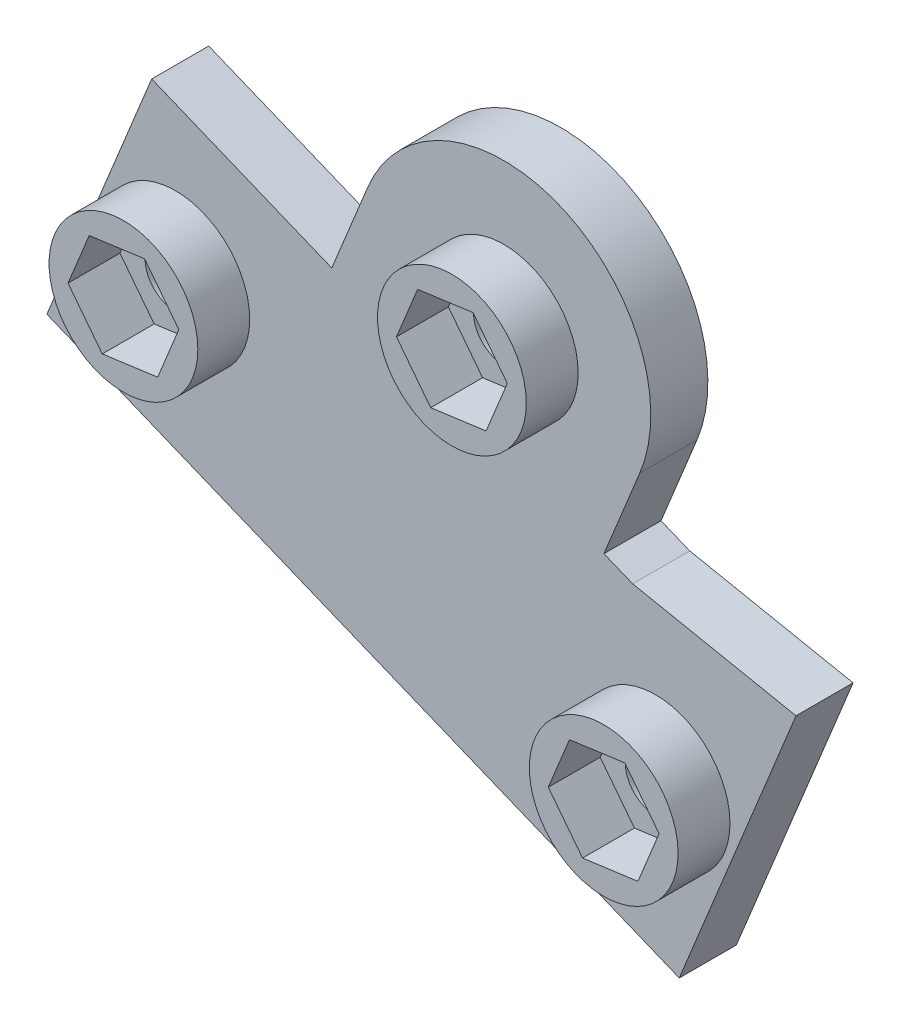
SolidWorks part; units mm, degrees
ref_plane "Front Plane" through (0, 0, 0) normal (0, 0, 1) x (1, 0, 0)
ref_plane "Top Plane" through (0, 0, 0) normal (0, 1, 0) x (1, 0, 0)
ref_plane "Right Plane" through (0, 0, 0) normal (1, 0, 0) x (0, 0, -1)
sketch "Sketch1" plane through (0, 0, 0) normal (0, 0, 1) x (1, 0, 0)
  line L0 (-67.8672, -11.1468) -> (-69.9439, -16.2233)
  line L1 (-52.1328, -17.5832) -> (-54.2095, -22.6598)
  line L2 (-86.4142, -26.7728) -> (-80.3564, -11.9639)
  line L3 (-49.8549, -41.7281) -> (-43.1038, -25.2247)
  line L6 (-68.0868, -16.983) -> (-80.5878, -11.8693)
  line L7 (-80.5878, -11.8693) -> (-86.6456, -26.6781)
  line L8 (-86.6456, -26.6781) -> (-49.6235, -41.8228)
  line L9 (-49.6235, -41.8228) -> (-42.8541, -25.2745)
  line L10 (-42.8541, -25.2745) -> (-52.5473, -23.3398)
  line L11 (-52.5473, -23.3398) -> (-56.0666, -21.9001)
  line L12 (-68.0868, -16.983) -> (-80.5878, -11.8693)
  line L13 (-80.5878, -11.8693) -> (-86.6456, -26.6781)
  line L14 (-86.6456, -26.6781) -> (-49.6235, -41.8228)
  line L15 (-49.6235, -41.8228) -> (-42.8541, -25.2745)
  line L16 (-42.8541, -25.2745) -> (-52.5473, -23.3398)
  line L17 (-52.5473, -23.3398) -> (-56.0666, -21.9001)
  circle A0 centre (-78.9889, -21.1668) radius 1.75 construction
  arc A1 (-68.0868, -16.983) -> (-56.0666, -21.9001) centre (-60, -14.365) ccw
  arc A2 (-68.0868, -16.983) -> (-56.0666, -21.9001) centre (-60, -14.365) ccw
  circle A3 centre (-51.2223, -32.5253) radius 1.75 construction
  circle A4 centre (-78.9889, -21.1668) radius 1.75
  circle A5 centre (-51.2223, -32.5253) radius 1.75
  circle A6 centre (-60, -14.365) radius 1.75
  circle A7 centre (-60, -14.365) radius 8.5
  dimension "D2" = 0.25
  dimension "D3" = 0.25
  dimension "D1" = 0
extrude "Boss-Extrude1" add sketch "Sketch1" along normal blind 3.3 contours A7 A2 A6 | A7 L0 L12 | A2 L12 L2 L14 L3 L16 L17 A5 A4 | A7 L17 L1 region at (-68.8941, -15.2085, 0) region at (-58.4065, -6.2606, 0) region at (-64.9518, -27.1084, 0) region at (-54.2471, -21.2002, 0)
sketch "Sketch2" plane through (0, 0, 0) normal (0, 0, -1) x (-1, 0, 0)
  circle A0 centre (60, -14.365) radius 4.1
  circle A1 centre (60, -14.365) radius 1.75 construction
  circle A2 centre (60, -14.365) radius 1.75
  dimension "D1" = 8.2
extrude "Boss-Extrude2" add sketch "Sketch2" along normal blind 0.2
sketch "Sketch3" plane through (0, 0, 3.3) normal (0, 0, 1) x (1, 0, 0)
  line L0 (-86.4142, -26.7728) -> (-80.3564, -11.9639) construction
  line L1 (-77.7648, -18.1743) -> (-80.9684, -18.6104)
  line L2 (-80.9684, -18.6104) -> (-82.1925, -21.6029)
  line L3 (-82.1925, -21.6029) -> (-80.213, -24.1592)
  line L4 (-80.213, -24.1592) -> (-77.0094, -23.7231)
  line L5 (-77.0094, -23.7231) -> (-75.7853, -20.7307)
  line L6 (-75.7853, -20.7307) -> (-77.7648, -18.1743)
  line L7 (-49.8549, -41.7281) -> (-43.1038, -25.2247) construction
  line L8 (-52.4464, -35.5177) -> (-49.2428, -35.0816)
  line L9 (-49.2428, -35.0816) -> (-48.0187, -32.0892)
  line L10 (-48.0187, -32.0892) -> (-49.9982, -29.5328)
  line L11 (-49.9982, -29.5328) -> (-53.2018, -29.9689)
  line L12 (-53.2018, -29.9689) -> (-54.4259, -32.9614)
  line L13 (-54.4259, -32.9614) -> (-52.4464, -35.5177)
  line L14 (-67.8672, -11.1468) -> (-69.9439, -16.2233) construction
  line L15 (-61.2241, -17.3575) -> (-58.0205, -16.9214)
  line L16 (-58.0205, -16.9214) -> (-56.7964, -13.9289)
  line L17 (-56.7964, -13.9289) -> (-58.7759, -11.3725)
  line L18 (-58.7759, -11.3725) -> (-61.9795, -11.8086)
  line L19 (-61.9795, -11.8086) -> (-63.2036, -14.8011)
  line L20 (-63.2036, -14.8011) -> (-61.2241, -17.3575)
  circle A0 centre (-78.9889, -21.1668) radius 2.8 construction
  circle A1 centre (-51.2223, -32.5253) radius 2.8 construction
  circle A2 centre (-60, -14.365) radius 2.8 construction
  circle A3 centre (-78.9889, -21.1668) radius 4.3
  circle A4 centre (-60, -14.365) radius 4.3
  circle A5 centre (-51.2223, -32.5253) radius 4.3
  dimension "D2" = 8.6
  dimension "D1" = 5.6
extrude "Boss-Extrude3" add sketch "Sketch3" along normal blind 3 contours A3 L6 L5 L4 L3 L2 L1 | A4 L20 L19 L18 L17 L16 L15 | A5 L13 L12 L11 L10 L9 L8 region at (-83.1673, -21.1668, 3.3) region at (-64.1784, -14.365, 3.3) region at (-55.4007, -32.5253, 3.3)
